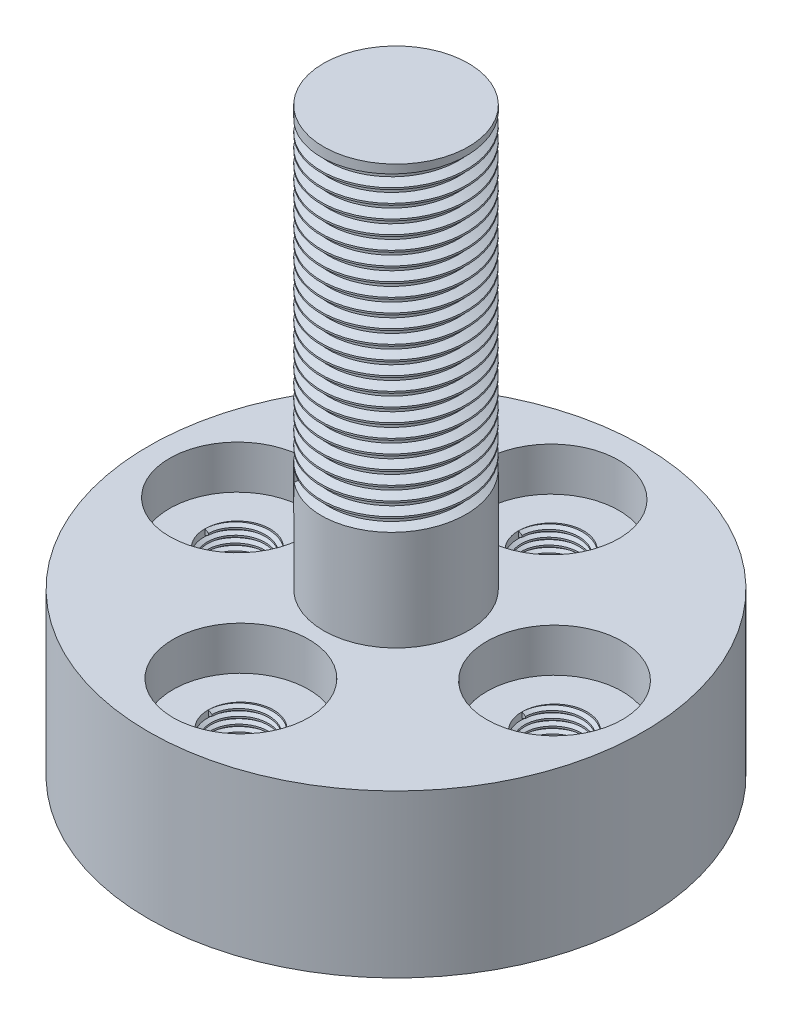
SolidWorks part; units mm, degrees
material "Plain Carbon Steel"
ref_plane "Front Plane" through (0, 0, 0) normal (0, 0, 1) x (1, 0, 0)
ref_plane "Top Plane" through (0, 0, 0) normal (0, 1, 0) x (1, 0, 0)
ref_plane "Right Plane" through (0, 0, 0) normal (1, 0, 0) x (0, 0, -1)
sketch "Sketch1" plane through (0, 0, 0) normal (0, 1, 0) x (1, 0, 0)
  circle A0 centre (0, 0) radius 9.1186
  dimension "D1" = 18.2372
extrude "Boss-Extrude1" add sketch "Sketch1" along normal blind 5.969 contours A0
sketch "Sketch2" plane through (0, 5.969, 0) normal (0, 1, 0) x (1, 0, 0)
  circle A0 centre (0, 0) radius 2.667
  dimension "D1" = 5.334
extrude "Boss-Extrude2" add sketch "Sketch2" along normal blind 15.4432 contours A0
thread "Thread1" pitch 0.5 method cut profile "Thread Profile1" start angle 0, offset 0, length 11.43, pitch 0.5, diameter 5.334
ref_plane "Plane1" through (-2.667, 21.4122, 0) normal (0, 0, 1) x (-1, 0, 0)
sketch "Thread Profile1" plane through (-2.667, 21.4122, 0) normal (0, 0, 1) x (-1, 0, 0)
  line L0 (0, 0) -> (0, 0.5) construction
  line L11 (0, 0) -> (0, 0.4375)
  line L12 (0, 0.4375) -> (-0.2706, 0.2812)
  line L13 (-0.2706, 0.2812) -> (-0.2706, 0.1562)
  line L15 (-0.2706, 0.1562) -> (0, 0)
  line L17 (-0.2706, 0.2187) -> (0, 0.2187) construction
  point P2 (0, 0)
  dimension "Pitch" = 0.5
  dimension "Profile_Angle" = 60
  dimension "Profile_Land" = 0.125
  dimension "Profile_Height" = 0.2706
sketch "Sketch5" plane through (0, 5.969, 0) normal (0, 1, 0) x (1, 0, 0)
  line L0 (-10.0305, 0) -> (10.0305, 0) construction
  line L1 (0, -10.0305) -> (0, 10.0305) construction
  point P0 (0, 5.715)
  point P7 (0, -5.715)
  point P9 (5.842, 0)
  point P17 (-5.842, 0)
  dimension "D1" = 5.715
  dimension "D2" = 5.842
hole_wizard "CBORE for M2 Pan Head Screw1" positions "Sketch5" profile "Sketch6" counterbore size "M2" standard "ISO" end condition through all
sketch "Sketch6" plane through (0, 5.969, -5.715) normal (1, 0, 0) x (0, 0, 1)
  line L0 (0, 0) -> (0, 5.969)
  line L1 (0, 5.969) -> (1.2, 5.969)
  line L3 (1.2, 5.969) -> (1.2, 1.6)
  line L4 (1.2, 1.6) -> (2.5, 1.6)
  line L5 (2.5, 1.6) -> (2.5, 0)
  line L7 (2.5, 0) -> (0, 0)
  line L11 (0, -6.35) -> (0, 107.95) construction
  dimension "Thru Hole Dia." = 2.4
  dimension "Thru Hole Depth" = 5.969
  dimension "C'Bore Dia." = 5
  dimension "C'Bore Depth" = 1.6
sketch "Sketch7" plane through (0, 0, 0) normal (0, -1, 0) x (1, 0, 0)
  circle A0 centre (0, 0) radius 2
  dimension "D1" = 4
extrude "Cut-Extrude1" cut sketch "Sketch7" against normal blind 6 contours A0
thread "Thread2" pitch 0.25 method extrude profile "Thread Profile7" start angle 0, offset 0, length 4.064, pitch 0.25, diameter 2.4
ref_plane "Plane7" through (-1.2, 4.369, 5.715) normal (0, 0, 1) x (-1, 0, 0)
sketch "Thread Profile7" plane through (-1.2, 4.369, 5.715) normal (0, 0, 1) x (-1, 0, 0)
  line L0 (0, 0) -> (0, 0.25) construction
  line L11 (0, 0) -> (0, 0.2187)
  line L12 (0, 0.2187) -> (-0.1353, 0.1406)
  line L13 (-0.1353, 0.1406) -> (-0.1353, 0.0781)
  line L15 (-0.1353, 0.0781) -> (0, 0)
  line L17 (-0.1353, 0.1094) -> (0, 0.1094) construction
  point P2 (0, 0)
  dimension "Pitch" = 0.25
  dimension "Profile_Angle" = 60
  dimension "Profile_Land" = 0.0625
  dimension "Profile_Height" = 0.1353
thread "Thread3" pitch 0.25 method extrude profile "Thread Profile8" start angle 0, offset 0, length 4.064, pitch 0.25, diameter 2.4
ref_plane "Plane8" through (-7.042, 4.369, 0) normal (0, 0, 1) x (-1, 0, 0)
sketch "Thread Profile8" plane through (-7.042, 4.369, 0) normal (0, 0, 1) x (-1, 0, 0)
  line L0 (0, 0) -> (0, 0.25) construction
  line L11 (0, 0) -> (0, 0.2187)
  line L12 (0, 0.2187) -> (-0.1353, 0.1406)
  line L13 (-0.1353, 0.1406) -> (-0.1353, 0.0781)
  line L15 (-0.1353, 0.0781) -> (0, 0)
  line L17 (-0.1353, 0.1094) -> (0, 0.1094) construction
  point P2 (0, 0)
  dimension "Pitch" = 0.25
  dimension "Profile_Angle" = 60
  dimension "Profile_Land" = 0.0625
  dimension "Profile_Height" = 0.1353
thread "Thread4" pitch 0.25 method extrude profile "Thread Profile9" start angle 0, offset 0, length 4.064, pitch 0.25, diameter 2.4
ref_plane "Plane9" through (4.642, 4.369, 0) normal (0, 0, 1) x (-1, 0, 0)
sketch "Thread Profile9" plane through (4.642, 4.369, 0) normal (0, 0, 1) x (-1, 0, 0)
  line L0 (0, 0) -> (0, 0.25) construction
  line L11 (0, 0) -> (0, 0.2187)
  line L12 (0, 0.2187) -> (-0.1353, 0.1406)
  line L13 (-0.1353, 0.1406) -> (-0.1353, 0.0781)
  line L15 (-0.1353, 0.0781) -> (0, 0)
  line L17 (-0.1353, 0.1094) -> (0, 0.1094) construction
  point P2 (0, 0)
  dimension "Pitch" = 0.25
  dimension "Profile_Angle" = 60
  dimension "Profile_Land" = 0.0625
  dimension "Profile_Height" = 0.1353
thread "Thread5" pitch 0.25 method extrude profile "Thread Profile10" start angle 0, offset 0, length 4.064, pitch 0.25, diameter 2.4
ref_plane "Plane10" through (-1.2, 4.369, -5.715) normal (0, 0, 1) x (-1, 0, 0)
sketch "Thread Profile10" plane through (-1.2, 4.369, -5.715) normal (0, 0, 1) x (-1, 0, 0)
  line L0 (0, 0) -> (0, 0.25) construction
  line L11 (0, 0) -> (0, 0.2187)
  line L12 (0, 0.2187) -> (-0.1353, 0.1406)
  line L13 (-0.1353, 0.1406) -> (-0.1353, 0.0781)
  line L15 (-0.1353, 0.0781) -> (0, 0)
  line L17 (-0.1353, 0.1094) -> (0, 0.1094) construction
  point P2 (0, 0)
  dimension "Pitch" = 0.25
  dimension "Profile_Angle" = 60
  dimension "Profile_Land" = 0.0625
  dimension "Profile_Height" = 0.1353
